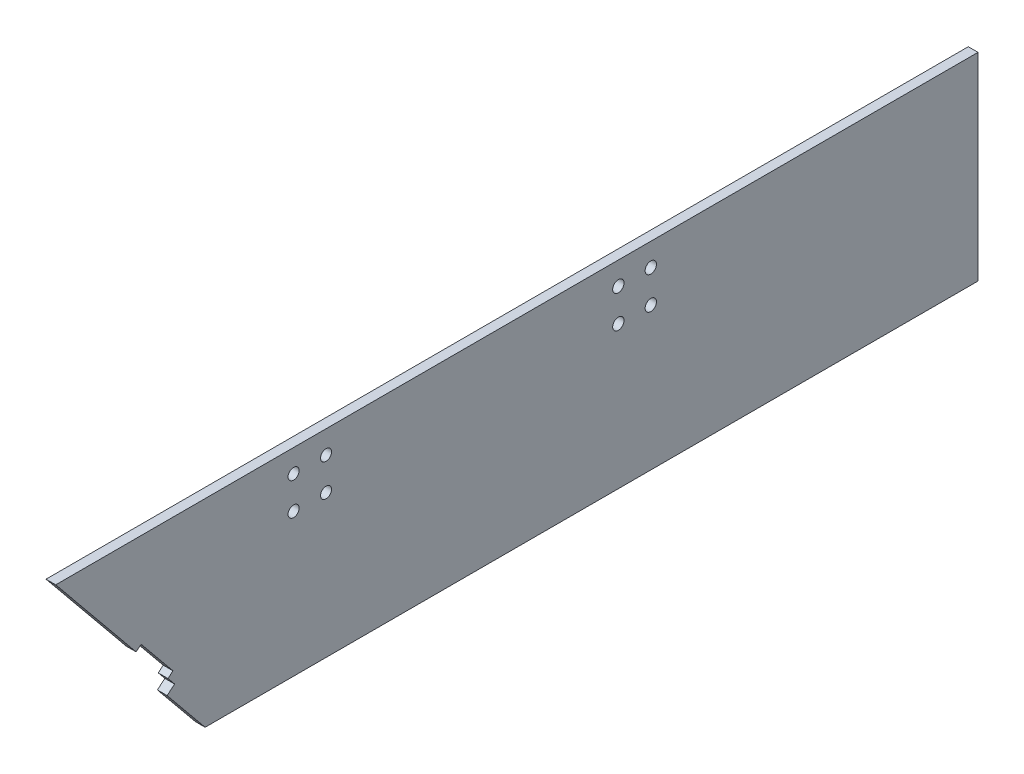
SolidWorks part; units mm, degrees
ref_plane "Front Plane" through (0, 0, 0) normal (0, 0, 1) x (1, 0, 0)
ref_plane "Top Plane" through (0, 0, 0) normal (0, 1, 0) x (1, 0, 0)
ref_plane "Right Plane" through (0, 0, 0) normal (1, 0, 0) x (0, 0, -1)
sketch "Sketch1" plane through (0, 0, 0) normal (0, 0, 1) x (1, 0, 0)
  line L0 (3, 76) -> (3, 0)
  line L2 (0, 0) -> (0, 76)
  line L5 (3, 0) -> (0, 0)
  line L6 (3, 76) -> (0, 76)
  dimension "D1" = 76
  dimension "D2" = 3
extrude "Boss-Extrude1" add sketch "Sketch1" along normal blind 220 contours L2 L0 region at (1.5, 38, 0)
hole_wizard "M3 Clearance Hole1" positions "Sketch2" profile "Sketch3" hole size "M3" standard "ANSI Metric" end condition through all
sketch "Sketch2" plane through (0, 0, 0) normal (-1, 0, 0) x (0, 0, 1)
  point P0 (50.7547, 59)
  point P3 (60.7547, 59)
  point P6 (60.7547, 69)
  point P9 (50.7547, 69)
  point P12 (200.7547, 59)
  point P15 (200.7547, 69)
  point P18 (210.7547, 59)
  point P21 (210.7547, 69)
sketch "Sketch3" plane through (0, 59, 50.7547) normal (0, 1, 0) x (0, 0, 1)
  line L0 (0, 0) -> (0, 3)
  line L1 (0, 3) -> (1.7, 3)
  line L2 (1.7, 3) -> (1.7, 0.025)
  line L3 (1.7, 0.025) -> (1.725, 0)
  line L5 (1.725, 0) -> (0, 0)
  line L6 (-1.7, 0.025) -> (-1.725, 0) construction
  line L11 (0, -6.35) -> (0, 107.95) construction
  dimension "Thru Hole Dia." = 3.4
  dimension "Thru Hole Depth" = 3
  dimension "Near C'Sink Dia." = 3.45
  dimension "Near C'Sink Angle" = 90
sketch "Sketch4" plane through (0, 0, 0) normal (-1, 0, 0) x (0, 0, 1)
  line L0 (220, 0) -> (220, 76) construction
  line L1 (0, 0) -> (220, 0)
  line L2 (0, 0) -> (0, 15)
  line L3 (0, 15) -> (220, 15)
  line L4 (220, 0) -> (220, 15)
  dimension "D1" = 15
extrude "Cut-Extrude1" cut sketch "Sketch4" against normal through all
sketch "Sketch5" plane through (0, 0, 0) normal (-1, 0, 0) x (0, 0, 1)
  line L0 (200.7547, 69) -> (110.7547, 69) construction
  line L2 (110.7547, 69) -> (100.7547, 69) construction
  line L3 (110.7547, 69) -> (110.7547, 59) construction
  line L4 (110.7547, 59) -> (100.7547, 59) construction
  line L5 (100.7547, 69) -> (100.7547, 59) construction
  circle A0 centre (200.7547, 69) radius 1.725 construction
  circle A1 centre (200.7547, 69) radius 1.725 construction
  circle A2 centre (110.7547, 69) radius 1.75
  circle A4 centre (100.7547, 69) radius 1.75
  circle A5 centre (100.7547, 59) radius 1.75
  circle A6 centre (110.7547, 59) radius 1.75
  dimension "D2" = 3.5
  dimension "D1" = 90
  dimension "D3" = 10
  dimension "D4" = 10
extrude "Cut-Extrude2" cut sketch "Sketch5" against normal through all
sketch "Sketch6" plane through (0, 0, 0) normal (-1, 0, 0) x (0, 0, 1)
  circle A0 centre (50.7547, 59) radius 1.725 construction
  circle A1 centre (60.7547, 59) radius 1.7 construction
  circle A2 centre (60.7547, 69) radius 1.725 construction
  circle A3 centre (50.7547, 69) radius 1.725 construction
  circle A4 centre (50.7547, 59) radius 1.725
  circle A5 centre (60.7547, 59) radius 1.7
  circle A6 centre (60.7547, 69) radius 1.725
  circle A7 centre (50.7547, 69) radius 1.725
extrude "Boss-Extrude2" add sketch "Sketch6" against normal blind 3
sketch "Sketch7" plane through (0, 0, 0) normal (-1, 0, 0) x (0, 0, 1)
  line L0 (220, 15) -> (0, 15) construction
  line L1 (220, 76) -> (284, 76)
  line L2 (220, 76) -> (220, 15)
  line L3 (220, 15) -> (238, 15)
  line L5 (249.7101, 29.3221) -> (247.3876, 31.2211)
  line L8 (249.7101, 29.3221) -> (238, 15)
  line L9 (247.3876, 31.2211) -> (249.4448, 33.7371)
  line L10 (249.4448, 33.7371) -> (247.8965, 35.0031)
  line L11 (247.8965, 35.0031) -> (257.7076, 47.0027)
  line L12 (257.7076, 47.0027) -> (259.256, 45.7367)
  line L13 (259.256, 45.7367) -> (284, 76)
  dimension "D1" = 64
  dimension "D2" = 18
  dimension "D3" = 3
  dimension "D4" = 18.5
  dimension "D5" = 2
  dimension "D6" = 3.25
  dimension "D7" = 15.5
extrude "Boss-Extrude3" add sketch "Sketch7" against normal blind 3
